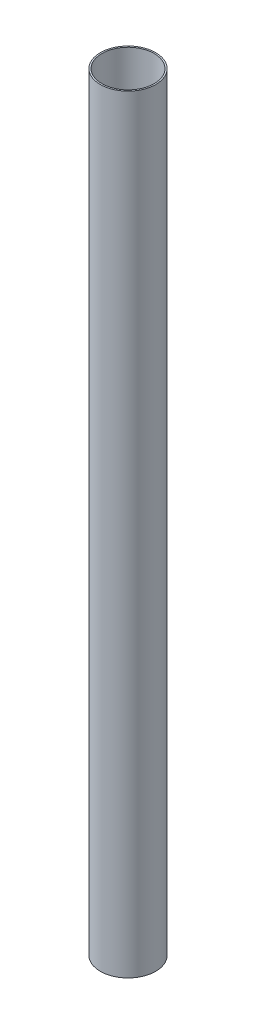
SolidWorks part; units mm, degrees
material "6063-T6"
ref_plane "Front Plane" through (0, 0, 0) normal (0, 0, 1) x (1, 0, 0)
ref_plane "Top Plane" through (0, 0, 0) normal (0, 1, 0) x (1, 0, 0)
ref_plane "Right Plane" through (0, 0, 0) normal (1, 0, 0) x (0, 0, -1)
sketch "Sketch1" plane through (0, 0, 0) normal (0, 0, 1) x (1, 0, 0)
  line L0 (0, 0) -> (0, 45.6531) construction
  line L1 (25.5143, 85.6926) -> (26.9875, 85.6926)
  line L2 (25.5143, 85.6926) -> (25.5143, -663.6074)
  line L3 (25.5143, -663.6074) -> (26.9875, -663.6074)
  line L4 (26.9875, 85.6926) -> (26.9875, -663.6074)
revolve "Revolve1" add sketch "Sketch1" angle 360 about L0
